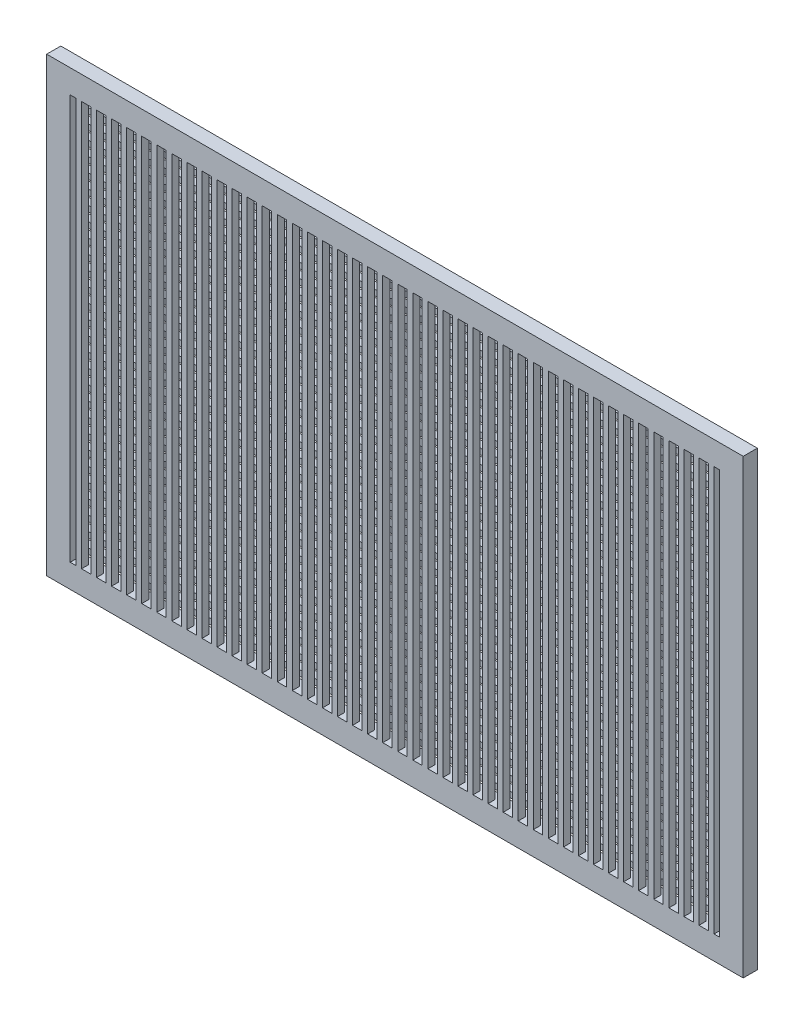
SolidWorks part; units mm, degrees
ref_plane "Front Plane" through (0, 0, 0) normal (0, 0, 1) x (1, 0, 0)
ref_plane "Top Plane" through (0, 0, 0) normal (0, 1, 0) x (1, 0, 0)
ref_plane "Right Plane" through (0, 0, 0) normal (1, 0, 0) x (0, 0, -1)
sketch "Sketch1" plane through (0, 0, 0) normal (0, 0, 1) x (1, 0, 0)
  line L10 (34.5, 21.5) -> (-34.5, 21.5)
  line L11 (-34.5, 21.5) -> (-34.5, -21.5)
  line L12 (-34.5, -21.5) -> (34.5, -21.5)
  line L13 (34.5, -21.5) -> (34.5, 21.5)
  line L14 (-37, -24) -> (37, -24)
  line L15 (-37, 24) -> (-37, -24)
  line L16 (37, 24) -> (-37, 24)
  line L17 (37, -24) -> (37, 24)
  line L18 (-37, -24) -> (37, -24)
  line L19 (-37, 24) -> (-37, -24)
  line L20 (37, 24) -> (-37, 24)
  line L21 (37, -24) -> (37, 24)
  point P4 (42.0379, -31.0773)
  point P9 (-36.9236, 32.9714)
  point P11 (37.1837, -37.1837)
  point P12 (34.8837, -34.8837)
  point P13 (37.1837, 37.1837)
  point P14 (30.3652, 30.3652)
  point P15 (25.9982, 25.9982)
  point P16 (19.1615, 19.1615)
  dimension "D2" = 2.5
  dimension "D1" = 0.2
extrude "Boss-Extrude1" add sketch "Sketch1" against normal blind 0.75 and the other way blind 0.75
sketch "Sketch2" plane through (0, 0, 0) normal (0, 0, 1) x (1, 0, 0)
  line L0 (0, -21.5) -> (0, 21.5) construction
  line L1 (-34.5, -19.95) -> (34.5, -19.95)
  line L2 (-34.5, -19.95) -> (-34.5, -20.55)
  line L3 (-34.5, -20.55) -> (34.5, -20.55)
  line L4 (34.5, -19.95) -> (34.5, -20.55)
  line L5 (34.5, 21.5) -> (-34.5, 21.5) construction
  line L6 (-34.5, -18.45) -> (-34.5, -19.05)
  line L7 (-34.5, -19.05) -> (34.5, -19.05)
  line L8 (-34.5, -18.45) -> (34.5, -18.45)
  line L9 (34.5, -18.45) -> (34.5, -19.05)
  line L10 (-34.5, -16.95) -> (-34.5, -17.55)
  line L11 (-34.5, -17.55) -> (34.5, -17.55)
  line L12 (-34.5, -16.95) -> (34.5, -16.95)
  line L13 (34.5, -16.95) -> (34.5, -17.55)
  line L14 (-34.5, -15.45) -> (-34.5, -16.05)
  line L15 (-34.5, -16.05) -> (34.5, -16.05)
  line L16 (-34.5, -15.45) -> (34.5, -15.45)
  line L17 (34.5, -15.45) -> (34.5, -16.05)
  line L18 (-34.5, -13.95) -> (-34.5, -14.55)
  line L19 (-34.5, -14.55) -> (34.5, -14.55)
  line L20 (-34.5, -13.95) -> (34.5, -13.95)
  line L21 (34.5, -13.95) -> (34.5, -14.55)
  line L22 (-34.5, -12.45) -> (-34.5, -13.05)
  line L23 (-34.5, -13.05) -> (34.5, -13.05)
  line L24 (-34.5, -12.45) -> (34.5, -12.45)
  line L25 (34.5, -12.45) -> (34.5, -13.05)
  line L26 (-34.5, -10.95) -> (-34.5, -11.55)
  line L27 (-34.5, -11.55) -> (34.5, -11.55)
  line L28 (-34.5, -10.95) -> (34.5, -10.95)
  line L29 (34.5, -10.95) -> (34.5, -11.55)
  line L30 (-34.5, -9.45) -> (-34.5, -10.05)
  line L31 (-34.5, -10.05) -> (34.5, -10.05)
  line L32 (-34.5, -9.45) -> (34.5, -9.45)
  line L33 (34.5, -9.45) -> (34.5, -10.05)
  line L34 (-34.5, -7.95) -> (-34.5, -8.55)
  line L35 (-34.5, -8.55) -> (34.5, -8.55)
  line L36 (-34.5, -7.95) -> (34.5, -7.95)
  line L37 (34.5, -7.95) -> (34.5, -8.55)
  line L38 (-34.5, -6.45) -> (-34.5, -7.05)
  line L39 (-34.5, -7.05) -> (34.5, -7.05)
  line L40 (-34.5, -6.45) -> (34.5, -6.45)
  line L41 (34.5, -6.45) -> (34.5, -7.05)
  line L42 (-34.5, -4.95) -> (-34.5, -5.55)
  line L43 (-34.5, -5.55) -> (34.5, -5.55)
  line L44 (-34.5, -4.95) -> (34.5, -4.95)
  line L45 (34.5, -4.95) -> (34.5, -5.55)
  line L46 (-34.5, -3.45) -> (-34.5, -4.05)
  line L47 (-34.5, -4.05) -> (34.5, -4.05)
  line L48 (-34.5, -3.45) -> (34.5, -3.45)
  line L49 (34.5, -3.45) -> (34.5, -4.05)
  line L50 (-34.5, -1.95) -> (-34.5, -2.55)
  line L51 (-34.5, -2.55) -> (34.5, -2.55)
  line L52 (-34.5, -1.95) -> (34.5, -1.95)
  line L53 (34.5, -1.95) -> (34.5, -2.55)
  line L54 (-34.5, -0.45) -> (-34.5, -1.05)
  line L55 (-34.5, -1.05) -> (34.5, -1.05)
  line L56 (-34.5, -0.45) -> (34.5, -0.45)
  line L57 (34.5, -0.45) -> (34.5, -1.05)
  line L58 (-34.5, 1.05) -> (-34.5, 0.45)
  line L59 (-34.5, 0.45) -> (34.5, 0.45)
  line L60 (-34.5, 1.05) -> (34.5, 1.05)
  line L61 (34.5, 1.05) -> (34.5, 0.45)
  line L62 (-34.5, 2.55) -> (-34.5, 1.95)
  line L63 (-34.5, 1.95) -> (34.5, 1.95)
  line L64 (-34.5, 2.55) -> (34.5, 2.55)
  line L65 (34.5, 2.55) -> (34.5, 1.95)
  line L66 (-34.5, 4.05) -> (-34.5, 3.45)
  line L67 (-34.5, 3.45) -> (34.5, 3.45)
  line L68 (-34.5, 4.05) -> (34.5, 4.05)
  line L69 (34.5, 4.05) -> (34.5, 3.45)
  line L70 (-34.5, 5.55) -> (-34.5, 4.95)
  line L71 (-34.5, 4.95) -> (34.5, 4.95)
  line L72 (-34.5, 5.55) -> (34.5, 5.55)
  line L73 (34.5, 5.55) -> (34.5, 4.95)
  line L74 (-34.5, 7.05) -> (-34.5, 6.45)
  line L75 (-34.5, 6.45) -> (34.5, 6.45)
  line L76 (-34.5, 7.05) -> (34.5, 7.05)
  line L77 (34.5, 7.05) -> (34.5, 6.45)
  line L78 (-34.5, 8.55) -> (-34.5, 7.95)
  line L79 (-34.5, 7.95) -> (34.5, 7.95)
  line L80 (-34.5, 8.55) -> (34.5, 8.55)
  line L81 (34.5, 8.55) -> (34.5, 7.95)
  line L82 (-34.5, 10.05) -> (-34.5, 9.45)
  line L83 (-34.5, 9.45) -> (34.5, 9.45)
  line L84 (-34.5, 10.05) -> (34.5, 10.05)
  line L85 (34.5, 10.05) -> (34.5, 9.45)
  line L86 (34.5, -21.5) -> (34.5, 21.5) construction
  line L87 (-34.5, 11.55) -> (-34.5, 10.95)
  line L88 (-34.5, 10.95) -> (34.5, 10.95)
  line L89 (-34.5, 11.55) -> (34.5, 11.55)
  line L90 (34.5, 11.55) -> (34.5, 10.95)
  line L91 (-34.5, 13.05) -> (-34.5, 12.45)
  line L92 (-34.5, 12.45) -> (34.5, 12.45)
  line L93 (-34.5, 13.05) -> (34.5, 13.05)
  line L94 (34.5, 13.05) -> (34.5, 12.45)
  line L95 (-34.5, 14.55) -> (-34.5, 13.95)
  line L96 (-34.5, 13.95) -> (34.5, 13.95)
  line L97 (-34.5, 14.55) -> (34.5, 14.55)
  line L98 (34.5, 14.55) -> (34.5, 13.95)
  line L99 (-34.5, 16.05) -> (-34.5, 15.45)
  line L100 (-34.5, 15.45) -> (34.5, 15.45)
  line L101 (-34.5, 16.05) -> (34.5, 16.05)
  line L102 (34.5, 16.05) -> (34.5, 15.45)
  line L103 (-34.5, 17.55) -> (-34.5, 16.95)
  line L104 (-34.5, 16.95) -> (34.5, 16.95)
  line L105 (-34.5, 17.55) -> (34.5, 17.55)
  line L106 (34.5, 17.55) -> (34.5, 16.95)
  line L107 (-34.5, 19.05) -> (-34.5, 18.45)
  line L108 (-34.5, 18.45) -> (34.5, 18.45)
  line L109 (-34.5, 19.05) -> (34.5, 19.05)
  line L110 (34.5, 19.05) -> (34.5, 18.45)
  line L111 (-34.5, 20.55) -> (-34.5, 19.95)
  line L112 (-34.5, 19.95) -> (34.5, 19.95)
  line L113 (-34.5, 20.55) -> (34.5, 20.55)
  line L114 (34.5, 20.55) -> (34.5, 19.95)
  line L115 (-34.5, -19.95) -> (-34.5, -18.45) construction
  line L116 (0, 21.5) -> (0, 20.55) construction
  line L117 (0, -21.5) -> (0, -20.55) construction
  line L123 (-34.5, 21.5) -> (-34.5, -21.5) construction
  line L124 (-34.5, -21.5) -> (34.5, -21.5) construction
  point P0 (-34.5, 0.45)
  point P10 (0, 20.55)
  point P122 (-34.5, -20.55)
  point P125 (0, -20.55)
  point P126 (34.5, -20.55)
  point P128 (0, 0)
  point P131 (0, 0)
  dimension "D1" = 0.6
  dimension "D4" = 1.5
  dimension "D2" = 28
extrude "Boss-Extrude2" add sketch "Sketch2" against normal blind 0.75
sketch "Sketch3" plane through (0, 0, 0) normal (0, 0, 1) x (1, 0, 0)
  line L0 (34.5, 21.5) -> (-34.5, 21.5) construction
  line L1 (-33.9, 21.5) -> (-33.3, 21.5)
  line L2 (-33.9, 21.5) -> (-33.9, -21.5)
  line L3 (-33.9, -21.5) -> (-33.3, -21.5)
  line L4 (-33.3, 21.5) -> (-33.3, -21.5)
  line L5 (-34.5, -21.5) -> (34.5, -21.5) construction
  line L6 (-34.5, 0) -> (34.5, 0) construction
  line L7 (-34.5, 21.5) -> (-34.5, -21.5) construction
  line L8 (34.5, -21.5) -> (34.5, 21.5) construction
  line L9 (-32.3, 21.5) -> (-32.3, -21.5)
  line L10 (-32.3, 21.5) -> (-31.7, 21.5)
  line L11 (-31.7, 21.5) -> (-31.7, -21.5)
  line L12 (-32.3, -21.5) -> (-31.7, -21.5)
  line L13 (-30.7, 21.5) -> (-30.7, -21.5)
  line L14 (-30.7, 21.5) -> (-30.1, 21.5)
  line L15 (-30.1, 21.5) -> (-30.1, -21.5)
  line L16 (-30.7, -21.5) -> (-30.1, -21.5)
  line L17 (-29.1, 21.5) -> (-29.1, -21.5)
  line L18 (-29.1, 21.5) -> (-28.5, 21.5)
  line L19 (-28.5, 21.5) -> (-28.5, -21.5)
  line L20 (-29.1, -21.5) -> (-28.5, -21.5)
  line L21 (-27.5, 21.5) -> (-27.5, -21.5)
  line L22 (-27.5, 21.5) -> (-26.9, 21.5)
  line L23 (-26.9, 21.5) -> (-26.9, -21.5)
  line L24 (-27.5, -21.5) -> (-26.9, -21.5)
  line L25 (-25.9, 21.5) -> (-25.9, -21.5)
  line L26 (-25.9, 21.5) -> (-25.3, 21.5)
  line L27 (-25.3, 21.5) -> (-25.3, -21.5)
  line L28 (-25.9, -21.5) -> (-25.3, -21.5)
  line L29 (-24.3, 21.5) -> (-24.3, -21.5)
  line L30 (-24.3, 21.5) -> (-23.7, 21.5)
  line L31 (-23.7, 21.5) -> (-23.7, -21.5)
  line L32 (-24.3, -21.5) -> (-23.7, -21.5)
  line L33 (-22.7, 21.5) -> (-22.7, -21.5)
  line L34 (-22.7, 21.5) -> (-22.1, 21.5)
  line L35 (-22.1, 21.5) -> (-22.1, -21.5)
  line L36 (-22.7, -21.5) -> (-22.1, -21.5)
  line L37 (-21.1, 21.5) -> (-21.1, -21.5)
  line L38 (-21.1, 21.5) -> (-20.5, 21.5)
  line L39 (-20.5, 21.5) -> (-20.5, -21.5)
  line L40 (-21.1, -21.5) -> (-20.5, -21.5)
  line L41 (-19.5, 21.5) -> (-19.5, -21.5)
  line L42 (-19.5, 21.5) -> (-18.9, 21.5)
  line L43 (-18.9, 21.5) -> (-18.9, -21.5)
  line L44 (-19.5, -21.5) -> (-18.9, -21.5)
  line L45 (-17.9, 21.5) -> (-17.9, -21.5)
  line L46 (-17.9, 21.5) -> (-17.3, 21.5)
  line L47 (-17.3, 21.5) -> (-17.3, -21.5)
  line L48 (-17.9, -21.5) -> (-17.3, -21.5)
  line L49 (-16.3, 21.5) -> (-16.3, -21.5)
  line L50 (-16.3, 21.5) -> (-15.7, 21.5)
  line L51 (-15.7, 21.5) -> (-15.7, -21.5)
  line L52 (-16.3, -21.5) -> (-15.7, -21.5)
  line L53 (-14.7, 21.5) -> (-14.7, -21.5)
  line L54 (-14.7, 21.5) -> (-14.1, 21.5)
  line L55 (-14.1, 21.5) -> (-14.1, -21.5)
  line L56 (-14.7, -21.5) -> (-14.1, -21.5)
  line L57 (-13.1, 21.5) -> (-13.1, -21.5)
  line L58 (-13.1, 21.5) -> (-12.5, 21.5)
  line L59 (-12.5, 21.5) -> (-12.5, -21.5)
  line L60 (-13.1, -21.5) -> (-12.5, -21.5)
  line L61 (-11.5, 21.5) -> (-11.5, -21.5)
  line L62 (-11.5, 21.5) -> (-10.9, 21.5)
  line L63 (-10.9, 21.5) -> (-10.9, -21.5)
  line L64 (-11.5, -21.5) -> (-10.9, -21.5)
  line L65 (-9.9, 21.5) -> (-9.9, -21.5)
  line L66 (-9.9, 21.5) -> (-9.3, 21.5)
  line L67 (-9.3, 21.5) -> (-9.3, -21.5)
  line L68 (-9.9, -21.5) -> (-9.3, -21.5)
  line L69 (-8.3, 21.5) -> (-8.3, -21.5)
  line L70 (-8.3, 21.5) -> (-7.7, 21.5)
  line L71 (-7.7, 21.5) -> (-7.7, -21.5)
  line L72 (-8.3, -21.5) -> (-7.7, -21.5)
  line L73 (-6.7, 21.5) -> (-6.7, -21.5)
  line L74 (-6.7, 21.5) -> (-6.1, 21.5)
  line L75 (-6.1, 21.5) -> (-6.1, -21.5)
  line L76 (-6.7, -21.5) -> (-6.1, -21.5)
  line L77 (-5.1, 21.5) -> (-5.1, -21.5)
  line L78 (-5.1, 21.5) -> (-4.5, 21.5)
  line L79 (-4.5, 21.5) -> (-4.5, -21.5)
  line L80 (-5.1, -21.5) -> (-4.5, -21.5)
  line L81 (-3.5, 21.5) -> (-3.5, -21.5)
  line L82 (-3.5, 21.5) -> (-2.9, 21.5)
  line L83 (-2.9, 21.5) -> (-2.9, -21.5)
  line L84 (-3.5, -21.5) -> (-2.9, -21.5)
  line L85 (-1.9, 21.5) -> (-1.9, -21.5)
  line L86 (-1.9, 21.5) -> (-1.3, 21.5)
  line L87 (-1.3, 21.5) -> (-1.3, -21.5)
  line L88 (-1.9, -21.5) -> (-1.3, -21.5)
  line L89 (-0.3, 21.5) -> (-0.3, -21.5)
  line L90 (-0.3, 21.5) -> (0.3, 21.5)
  line L91 (0.3, 21.5) -> (0.3, -21.5)
  line L92 (-0.3, -21.5) -> (0.3, -21.5)
  line L93 (1.3, 21.5) -> (1.3, -21.5)
  line L94 (1.3, 21.5) -> (1.9, 21.5)
  line L95 (1.9, 21.5) -> (1.9, -21.5)
  line L96 (1.3, -21.5) -> (1.9, -21.5)
  line L97 (2.9, 21.5) -> (2.9, -21.5)
  line L98 (2.9, 21.5) -> (3.5, 21.5)
  line L99 (3.5, 21.5) -> (3.5, -21.5)
  line L100 (2.9, -21.5) -> (3.5, -21.5)
  line L101 (4.5, 21.5) -> (4.5, -21.5)
  line L102 (4.5, 21.5) -> (5.1, 21.5)
  line L103 (5.1, 21.5) -> (5.1, -21.5)
  line L104 (4.5, -21.5) -> (5.1, -21.5)
  line L105 (6.1, 21.5) -> (6.1, -21.5)
  line L106 (6.1, 21.5) -> (6.7, 21.5)
  line L107 (6.7, 21.5) -> (6.7, -21.5)
  line L108 (6.1, -21.5) -> (6.7, -21.5)
  line L109 (7.7, 21.5) -> (7.7, -21.5)
  line L110 (7.7, 21.5) -> (8.3, 21.5)
  line L111 (8.3, 21.5) -> (8.3, -21.5)
  line L112 (7.7, -21.5) -> (8.3, -21.5)
  line L113 (9.3, 21.5) -> (9.3, -21.5)
  line L114 (9.3, 21.5) -> (9.9, 21.5)
  line L115 (9.9, 21.5) -> (9.9, -21.5)
  line L116 (9.3, -21.5) -> (9.9, -21.5)
  line L117 (10.9, 21.5) -> (10.9, -21.5)
  line L118 (10.9, 21.5) -> (11.5, 21.5)
  line L119 (11.5, 21.5) -> (11.5, -21.5)
  line L120 (10.9, -21.5) -> (11.5, -21.5)
  line L121 (12.5, 21.5) -> (12.5, -21.5)
  line L122 (12.5, 21.5) -> (13.1, 21.5)
  line L123 (13.1, 21.5) -> (13.1, -21.5)
  line L124 (12.5, -21.5) -> (13.1, -21.5)
  line L125 (14.1, 21.5) -> (14.1, -21.5)
  line L126 (14.1, 21.5) -> (14.7, 21.5)
  line L127 (14.7, 21.5) -> (14.7, -21.5)
  line L128 (14.1, -21.5) -> (14.7, -21.5)
  line L129 (15.7, 21.5) -> (15.7, -21.5)
  line L130 (15.7, 21.5) -> (16.3, 21.5)
  line L131 (16.3, 21.5) -> (16.3, -21.5)
  line L132 (15.7, -21.5) -> (16.3, -21.5)
  line L133 (17.3, 21.5) -> (17.3, -21.5)
  line L134 (17.3, 21.5) -> (17.9, 21.5)
  line L135 (17.9, 21.5) -> (17.9, -21.5)
  line L136 (17.3, -21.5) -> (17.9, -21.5)
  line L137 (18.9, 21.5) -> (18.9, -21.5)
  line L138 (18.9, 21.5) -> (19.5, 21.5)
  line L139 (19.5, 21.5) -> (19.5, -21.5)
  line L140 (18.9, -21.5) -> (19.5, -21.5)
  line L141 (20.5, 21.5) -> (20.5, -21.5)
  line L142 (20.5, 21.5) -> (21.1, 21.5)
  line L143 (21.1, 21.5) -> (21.1, -21.5)
  line L144 (20.5, -21.5) -> (21.1, -21.5)
  line L145 (22.1, 21.5) -> (22.1, -21.5)
  line L146 (22.1, 21.5) -> (22.7, 21.5)
  line L147 (22.7, 21.5) -> (22.7, -21.5)
  line L148 (22.1, -21.5) -> (22.7, -21.5)
  line L149 (23.7, 21.5) -> (23.7, -21.5)
  line L150 (23.7, 21.5) -> (24.3, 21.5)
  line L151 (24.3, 21.5) -> (24.3, -21.5)
  line L152 (23.7, -21.5) -> (24.3, -21.5)
  line L153 (25.3, 21.5) -> (25.3, -21.5)
  line L154 (25.3, 21.5) -> (25.9, 21.5)
  line L155 (25.9, 21.5) -> (25.9, -21.5)
  line L156 (25.3, -21.5) -> (25.9, -21.5)
  line L157 (26.9, 21.5) -> (26.9, -21.5)
  line L158 (26.9, 21.5) -> (27.5, 21.5)
  line L159 (27.5, 21.5) -> (27.5, -21.5)
  line L160 (26.9, -21.5) -> (27.5, -21.5)
  line L161 (28.5, 21.5) -> (28.5, -21.5)
  line L162 (28.5, 21.5) -> (29.1, 21.5)
  line L163 (29.1, 21.5) -> (29.1, -21.5)
  line L164 (28.5, -21.5) -> (29.1, -21.5)
  line L165 (30.1, 21.5) -> (30.1, -21.5)
  line L166 (30.1, 21.5) -> (30.7, 21.5)
  line L167 (30.7, 21.5) -> (30.7, -21.5)
  line L168 (30.1, -21.5) -> (30.7, -21.5)
  line L169 (31.7, 21.5) -> (31.7, -21.5)
  line L170 (31.7, 21.5) -> (32.3, 21.5)
  line L171 (32.3, 21.5) -> (32.3, -21.5)
  line L172 (31.7, -21.5) -> (32.3, -21.5)
  line L173 (33.3, 21.5) -> (33.3, -21.5)
  line L174 (33.3, 21.5) -> (33.9, 21.5)
  line L175 (33.9, 21.5) -> (33.9, -21.5)
  line L176 (33.3, -21.5) -> (33.9, -21.5)
  line L177 (34.5, 0) -> (33.9, 0) construction
  line L189 (-33.9, 0) -> (-34.5, 0) construction
  line L191 (34.9, 21.5) -> (34.9, -21.5) [skipped]
  line L192 (34.9, 21.5) -> (35.5, 21.5) [skipped]
  line L193 (35.5, 21.5) -> (35.5, -21.5) [skipped]
  line L194 (34.9, -21.5) -> (35.5, -21.5) [skipped]
  line L195 (36.5, 21.5) -> (36.5, -21.5) [skipped]
  line L196 (36.5, 21.5) -> (37.1, 21.5) [skipped]
  line L197 (37.1, 21.5) -> (37.1, -21.5) [skipped]
  line L198 (36.5, -21.5) -> (37.1, -21.5) [skipped]
  line L199 (38.1, 21.5) -> (38.1, -21.5) [skipped]
  line L200 (38.1, 21.5) -> (38.7, 21.5) [skipped]
  line L201 (38.7, 21.5) -> (38.7, -21.5) [skipped]
  line L202 (38.1, -21.5) -> (38.7, -21.5) [skipped]
  point P15 (-5.1, 21.5)
  dimension "D1" = 0.6
  dimension "D4" = 1
  dimension "D3" = 46
extrude "Boss-Extrude3" add sketch "Sketch3" along normal blind 0.75
